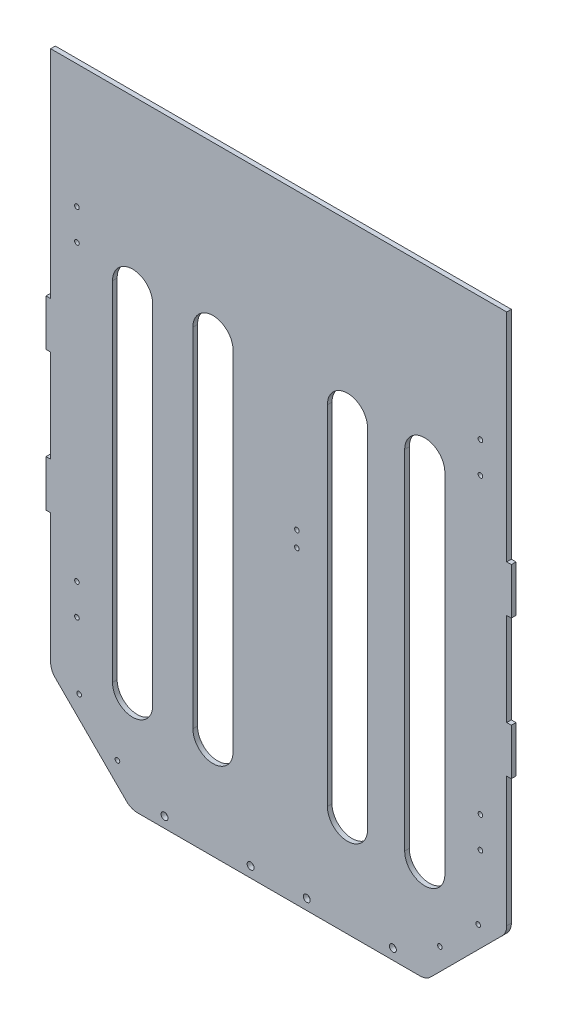
SolidWorks part; units mm, degrees
ref_plane "前视基准面" through (0, 0, 0) normal (0, 0, 1) x (1, 0, 0)
ref_plane "上视基准面" through (0, 0, 0) normal (0, 1, 0) x (1, 0, 0)
ref_plane "右视基准面" through (0, 0, 0) normal (1, 0, 0) x (0, 0, -1)
sketch "草图1" plane through (0, 0, 0) normal (0, 0, 1) x (1, 0, 0)
  line L0 (-147.5, 90) -> (-150.5, 90)
  line L1 (-147.5, 170) -> (147.5, 170)
  line L2 (-147.5, 170) -> (-147.5, 90)
  line L3 (-147.5, -170) -> (147.5, -170)
  line L4 (147.5, 170) -> (147.5, 90)
  line L5 (-147.5, 170) -> (147.5, -170) construction
  line L6 (-147.5, -170) -> (147.5, 170) construction
  line L7 (-150.5, 90) -> (-150.5, 60)
  line L8 (-150.5, 60) -> (-147.5, 60)
  line L9 (-147.5, 60) -> (-147.5, 0)
  line L10 (-147.5, 0) -> (-150.5, 0)
  line L11 (-150.5, 0) -> (-150.5, -30)
  line L12 (-150.5, -30) -> (-147.5, -30)
  line L13 (-147.5, -90) -> (-150.5, -90) construction
  line L14 (-150.5, -90) -> (-150.5, -120) construction
  line L15 (-150.5, -120) -> (-147.5, -120) construction
  line L16 (-147.5, -30) -> (-147.5, -90)
  line L17 (-147.5, -120) -> (-147.5, -170)
  line L18 (0, 0) -> (0, 121.9272) construction
  line L19 (147.5, -90) -> (150.5, -90) construction
  line L20 (150.5, -90) -> (150.5, -120) construction
  line L21 (150.5, -120) -> (147.5, -120) construction
  line L22 (147.5, 0) -> (150.5, 0)
  line L23 (150.5, 0) -> (150.5, -30)
  line L24 (150.5, -30) -> (147.5, -30)
  line L25 (147.5, 90) -> (150.5, 90)
  line L26 (150.5, 90) -> (150.5, 60)
  line L27 (150.5, 60) -> (147.5, 60)
  line L28 (147.5, -120) -> (147.5, -170)
  line L29 (147.5, -30) -> (147.5, -90)
  line L30 (147.5, 60) -> (147.5, 0)
  line L31 (-147.5, -90) -> (-147.5, -120)
  line L32 (147.5, -90) -> (147.5, -120)
  point P0 (0, 0)
  dimension "D1" = 295
  dimension "D2" = 340
  dimension "D3" = 30
  dimension "D4" = 3
  dimension "D5" = 80
  dimension "D6" = 3
  dimension "D7" = 30
  dimension "D8" = 30
  dimension "D9" = 3
  dimension "D10" = 50
  dimension "D11" = 60
extrude "凸台-拉伸1" add sketch "草图1" along normal blind 3
sketch "草图3" plane through (0, 0, 3) normal (0, 0, 1) x (1, 0, 0)
  line L0 (-147.5, -118) -> (-95.5, -170)
  line L1 (-147.5, -30) -> (-147.5, -170) construction
  line L2 (-147.5, -170) -> (147.5, -170) construction
  line L3 (-95.5, -170) -> (-147.5, -170)
  line L4 (-147.5, -170) -> (-147.5, -118)
  line L5 (147.5, -170) -> (147.5, -118)
  line L6 (147.5, -170) -> (147.5, -30) construction
  line L7 (147.5, -118) -> (95.5, -170)
  line L8 (95.5, -170) -> (147.5, -170)
  dimension "D1" = 52
  dimension "D2" = 52
  dimension "D3" = 52
  dimension "D4" = 52
extrude "切除-拉伸2" cut sketch "草图3" against normal through all
fillet "圆角1" [suppressed] radius 5
sketch "草图2" plane through (0, 0, 3) normal (0, 0, 1) x (1, 0, 0)
  line L0 (-95.5, -170) -> (95.5, -170) construction
  line L1 (0, -170) -> (0, -88.9982) construction
  circle A2 centre (73.85, -163.15) radius 2.25 construction
  circle A3 centre (18.15, -163.15) radius 2.25 construction
  circle A4 centre (-73.85, -163.15) radius 2.25 construction
  circle A5 centre (-18.15, -163.15) radius 2.25 construction
  circle A6 centre (11.8005, 40) radius 1.5
  circle A7 centre (11.8005, 30) radius 1.5
  circle A8 centre (73.85, -163.15) radius 2.25 construction
  circle A9 centre (18.15, -163.15) radius 2.25 construction
  circle A10 centre (-73.85, -163.15) radius 2.25 construction
  circle A11 centre (-18.15, -163.15) radius 2.25 construction
  circle A12 centre (-73.85, -163.15) radius 2.25
  circle A13 centre (-18.15, -163.15) radius 2.25
  circle A14 centre (18.15, -163.15) radius 2.25
  circle A15 centre (73.85, -163.15) radius 2.25
  dimension "D1" = 4.5
  dimension "D2" = 4.5
  dimension "D5" = 3
  dimension "D6" = 3
  dimension "D3" = 55.7
  dimension "D4" = 18.15
extrude "切除-拉伸1" cut sketch "草图2" against normal blind 10
sketch "草图4" plane through (0, 0, 3) normal (0, 0, 1) x (1, 0, 0)
  line L0 (147.5, 170) -> (-147.5, 170) construction
  line L1 (147.5, 90) -> (147.5, 170) construction
  line L2 (147.5, -118) -> (147.5, -30) construction
  line L3 (0, 170) -> (0, 113.7599) construction
  circle A0 centre (130.5, 150) radius 1.5
  circle A1 centre (130.5, 130) radius 1.5
  circle A2 centre (130.5, -60) radius 1.5
  circle A3 centre (130.5, -80) radius 1.5
  circle A4 centre (-130.5, -80) radius 1.5
  circle A5 centre (-130.5, -60) radius 1.5
  circle A6 centre (-130.5, 130) radius 1.5
  circle A7 centre (-130.5, 150) radius 1.5
  dimension "D1" = 20
  dimension "D2" = 20
  dimension "D3" = 190
  dimension "D4" = 20
  dimension "D5" = 17
  dimension "D6" = 17
  dimension "D7" = 17
  dimension "D8" = 17
  dimension "D9" = 3
  dimension "D10" = 3
  dimension "D11" = 3
  dimension "D12" = 3
extrude "切除-拉伸3" cut sketch "草图4" against normal through all
sketch "草图5" plane through (0, 0, 3) normal (0, 0, 1) x (1, 0, 0)
  line L0 (-94.5, 120) -> (-94.5, -105) construction
  line L1 (-81.5, 120) -> (-81.5, -105)
  line L2 (-107.5, 120) -> (-107.5, -105)
  line L3 (147.5, 170) -> (-147.5, 170) construction
  line L4 (-147.5, 60) -> (-147.5, 0) construction
  line L5 (-42.5, 120) -> (-42.5, -105) construction
  line L6 (-29.5, 120) -> (-29.5, -105)
  line L7 (-55.5, 120) -> (-55.5, -105)
  line L8 (44.5, 120) -> (44.5, -105) construction
  line L9 (57.5, 120) -> (57.5, -105)
  line L10 (31.5, 120) -> (31.5, -105)
  line L11 (94.5, 120) -> (94.5, -105) construction
  line L12 (107.5, 120) -> (107.5, -105)
  line L13 (81.5, 120) -> (81.5, -105)
  arc A0 (-81.5, 120) -> (-107.5, 120) centre (-94.5, 120) ccw
  arc A1 (-107.5, -105) -> (-81.5, -105) centre (-94.5, -105) ccw
  arc A2 (-29.5, 120) -> (-55.5, 120) centre (-42.5, 120) ccw
  arc A3 (-55.5, -105) -> (-29.5, -105) centre (-42.5, -105) ccw
  arc A4 (57.5, 120) -> (31.5, 120) centre (44.5, 120) ccw
  arc A5 (31.5, -105) -> (57.5, -105) centre (44.5, -105) ccw
  arc A6 (107.5, 120) -> (81.5, 120) centre (94.5, 120) ccw
  arc A7 (81.5, -105) -> (107.5, -105) centre (94.5, -105) ccw
  point P2 (-94.5, 7.5)
  point P14 (-42.5, 7.5)
  point P22 (44.5, 7.5)
  point P29 (94.5, 7.5)
  dimension "D1" = 13
  dimension "D2" = 225
  dimension "D3" = 50
  dimension "D4" = 53
  dimension "D8" = 52
  dimension "D9" = 87
  dimension "D5" = 2
  dimension "D6" = 2
  dimension "D7" = 2
extrude "切除-拉伸4" cut sketch "草图5" against normal through all
sketch "草图6" plane through (0, 0, 3) normal (0, 0, 1) x (1, 0, 0)
  line L0 (31.5, 120) -> (31.5, -105) construction
  line L1 (31.5, 12) -> (57.5, 12)
  line L2 (31.5, 12) -> (31.5, -23)
  line L3 (31.5, -23) -> (57.5, -23)
  line L4 (57.5, 12) -> (57.5, -23)
  line L5 (57.5, -105) -> (57.5, 120) construction
  arc A0 (57.5, 120) -> (31.5, 120) centre (44.5, 120) ccw construction
  dimension "D1" = 35
  dimension "D2" = 108
fillet "圆角3" radius 10 4 edges at (147.5, -118, 1.5) (95.5, -170, 1.5) (-95.5, -170, 1.5) (-147.5, -118, 1.5)
sketch "草图8" plane through (0, 0, 3) normal (0, 0, 1) x (1, 0, 0)
  line L0 (-129.0441, -122.3138) -> (-104.2954, -147.0625) construction
  line L1 (-98.4289, -167.0711) -> (-144.5711, -120.9289) construction
  line L2 (-147.5, -99.7493) -> (147.5, -99.7493) construction
  line L3 (-147.5, -30) -> (-147.5, -113.8579) construction
  line L4 (147.5, -113.8579) -> (147.5, -30) construction
  line L5 (0, -99.7493) -> (0, -54.3911) construction
  line L6 (129.0441, -122.3138) -> (104.2954, -147.0625) construction
  circle A0 centre (-129.0441, -122.3138) radius 1.5
  circle A1 centre (-104.2954, -147.0625) radius 1.5
  circle A2 centre (104.2954, -147.0625) radius 1.5
  circle A3 centre (129.0441, -122.3138) radius 1.5
  dimension "D1" = 3
  dimension "D2" = 3
  dimension "D3" = 10
  dimension "D4" = 35
extrude "切除-拉伸5" cut sketch "草图8" against normal through all
sketch "草图9" plane through (0, 0, 3) normal (0, 0, 1) x (1, 0, 0)
  line L1 (147.5, 170) -> (-147.5, 170)
  line L2 (147.5, 170) -> (147.5, 230)
  line L3 (147.5, 230) -> (-147.5, 230)
  line L4 (-147.5, 170) -> (-147.5, 230)
  dimension "D1" = 60
extrude "凸台-拉伸2" add sketch "草图9" against normal blind 3
